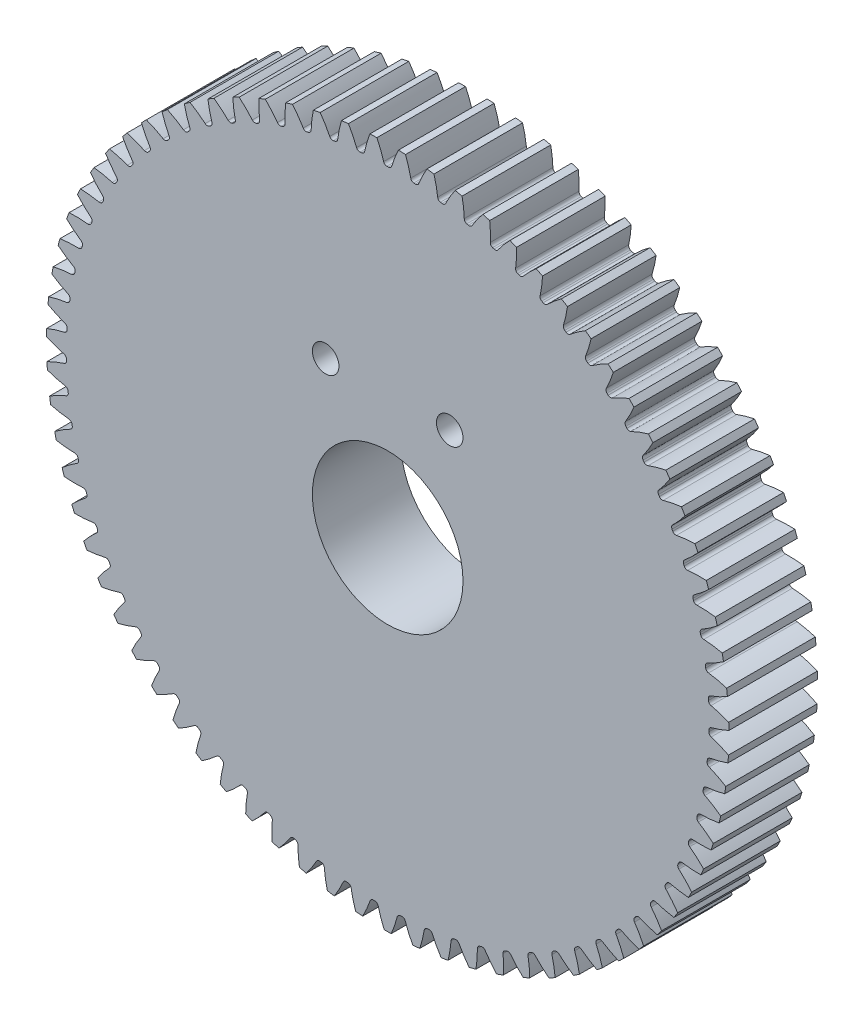
SolidWorks part; units mm, degrees
ref_plane "Front" through (0, 0, 0) normal (0, 0, 1) x (1, 0, 0)
ref_plane "Top" through (0, 0, 0) normal (0, 1, 0) x (1, 0, 0)
ref_plane "Right" through (0, 0, 0) normal (1, 0, 0) x (0, 0, -1)
ref_axis "Axis1" through (0, 0, -80.9) along (0, 0, 1)
sketch "草图1" plane through (0, 0, 0) normal (0, 0, 1) x (1, 0, 0)
  circle A0 centre (0, 0) radius 38.5
extrude "LaShenA" add sketch "草图1" along normal blind 10
sketch "SketchA" plane through (0, 0, 10) normal (0, 0, 1) x (1, 0, 0)
  line L0 (0, 0) -> (0, 38.5) construction
  arc A0 (0.0916, 36.2499) -> (-0.0916, 36.2499) centre (0, 0) ccw
  arc A1 (1.4788, 39.0083) -> (-1.4788, 39.0083) centre (0, 0) ccw
  arc A2 (-0.0916, 36.2499) -> (-0.4576, 36.5243) centre (-0.0925, 36.6299) cw
  arc A3 (0.4576, 36.5243) -> (0.0916, 36.2499) centre (0.0925, 36.6299) cw
  circle A4 centre (0, 0) radius 35.2385 construction
  circle A5 centre (0, 0) radius 38.5 construction
  circle A6 centre (0, 0) radius 36.25 construction
  circle A7 centre (0, 0) radius 37.5 construction
  spline S0 degree 3 poles (0.4576, 36.5243) (0.4608, 36.5355) (0.4704, 36.5685) (0.4866, 36.6238) (0.5068, 36.6905) (0.5279, 36.7588) (0.5499, 36.8285) (0.573, 36.8996) (0.5971, 36.9722) (0.6222, 37.0462) (0.6484, 37.1216) (0.6757, 37.1984) (0.7041, 37.2766) (0.7336, 37.3561) (0.7642, 37.437) (0.796, 37.5193) (0.829, 37.6029) (0.8632, 37.6879) (0.8986, 37.7741) (0.9352, 37.8617) (0.9731, 37.9505) (1.0123, 38.0406) (1.0528, 38.132) (1.0947, 38.2246) (1.1378, 38.3185) (1.1823, 38.4136) (1.2282, 38.5099) (1.2755, 38.6073) (1.3242, 38.706) (1.3915, 38.8401) (1.4435, 38.9409) (1.4788, 39.0083) knots 0.096666 0.096666 0.096666 0.096666 0.108398 0.131256 0.154677 0.178662 0.20321 0.228321 0.253996 0.280234 0.307036 0.334401 0.362329 0.39082 0.419875 0.449493 0.479675 0.51042 0.541728 0.5736 0.606035 0.639033 0.672595 0.70672 0.741408 0.77666 0.812475 0.848853 0.885795 0.9233 1 1 1 1
  spline S1 degree 3 poles (-0.4576, 36.5243) (-0.4608, 36.5355) (-0.4704, 36.5685) (-0.4866, 36.6238) (-0.5068, 36.6905) (-0.5279, 36.7588) (-0.5499, 36.8285) (-0.573, 36.8996) (-0.5971, 36.9722) (-0.6222, 37.0462) (-0.6484, 37.1216) (-0.6757, 37.1984) (-0.7041, 37.2766) (-0.7336, 37.3561) (-0.7642, 37.437) (-0.796, 37.5193) (-0.829, 37.6029) (-0.8632, 37.6879) (-0.8986, 37.7741) (-0.9352, 37.8617) (-0.9731, 37.9505) (-1.0123, 38.0406) (-1.0528, 38.132) (-1.0947, 38.2246) (-1.1378, 38.3185) (-1.1823, 38.4136) (-1.2282, 38.5099) (-1.2755, 38.6073) (-1.3242, 38.706) (-1.3915, 38.8401) (-1.4435, 38.9409) (-1.4788, 39.0083) knots 0.096666 0.096666 0.096666 0.096666 0.108398 0.131256 0.154677 0.178662 0.20321 0.228321 0.253996 0.280234 0.307036 0.334401 0.362329 0.39082 0.419875 0.449493 0.479675 0.51042 0.541728 0.5736 0.606035 0.639033 0.672595 0.70672 0.741408 0.77666 0.812475 0.848853 0.885795 0.9233 1 1 1 1
  dimension "D1" = 0.38
  dimension "Db" = 70.4769
  dimension "Da" = 77
  dimension "Df" = 72.5
  dimension "Dn" = 75
extrude "Cut-ExtrudeA" cut sketch "SketchA" against normal blind 30
pattern_circular "阵列(圆周)1" count 75 over 360 about axis through (0, 0, -80.9) along (0, 0, 1) of "Cut-ExtrudeA"
sketch "草图3" plane through (0, 0, 10) normal (0, 0, 1) x (1, 0, 0)
  line L0 (0, 0) -> (0, 4) construction
  line L1 (0, 4) -> (7, 4) construction
  line L2 (0, 4) -> (-7, 4) construction
  line L3 (-7, 4) -> (-7, 14) construction
  line L4 (7, 4) -> (7, 14) construction
  circle A0 centre (0, 0) radius 8.5
  circle A1 centre (-7, 14) radius 1.5
  circle A2 centre (7, 14) radius 1.5
  dimension "D1" = 4
  dimension "D4" = 10
  dimension "D6" = 17
  dimension "D2" = 7
  dimension "D3" = 7
  dimension "D5" = 10
extrude "切除-拉伸2" cut sketch "草图3" against normal blind 10
